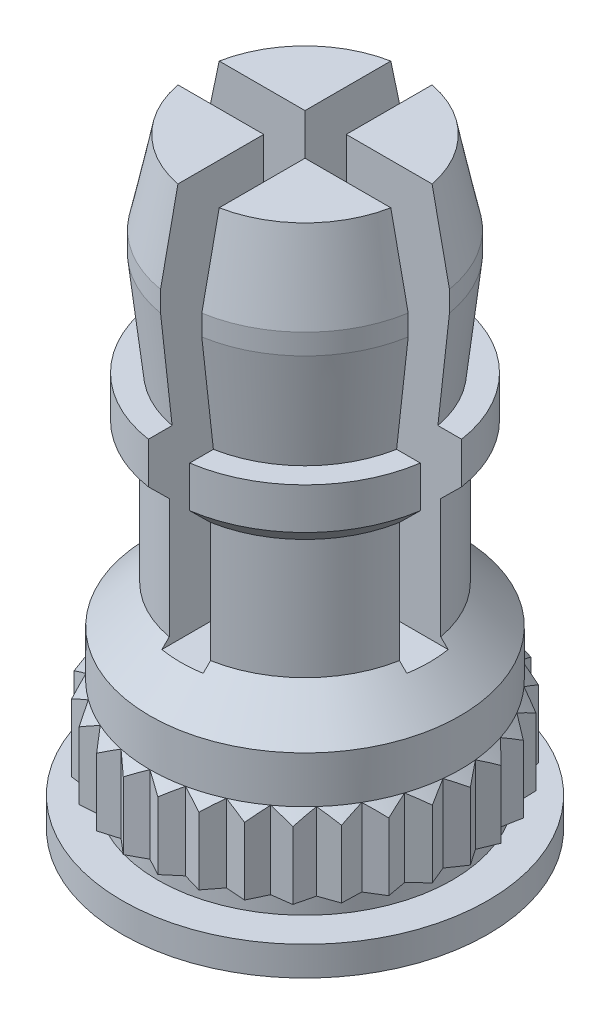
SolidWorks part; units mm, degrees
revolve "Body" add sketch "BodySke" angle 360 about L9 other way angle 12
sketch "BodySke" plane through (0, 0, 0) normal (0, 0, 1) x (1, 0, 0)
  line L0 (2.5578, 0) -> (2.5578, 0.381)
  line L1 (2.6924, 2.5354) -> (2.0295, 3.1984)
  line L2 (2.8702, 1.5494) -> (2.6924, 1.7272)
  line L3 (2.0295, 3.1984) -> (2.0295, 5.2756)
  line L4 (0, -0.508) -> (3.175, -0.508)
  line L5 (3.175, -0.508) -> (3.175, 0)
  line L6 (3.175, 0) -> (2.5578, 0)
  line L7 (2.3876, 5.6337) -> (2.3876, 6.35)
  line L8 (2.6924, 1.7272) -> (2.6924, 2.5354)
  line L9 (0, -0.508) -> (0, 17.145) construction
  line L10 (2.3876, 6.35) -> (1.9812, 6.35)
  line L11 (1.9812, 6.35) -> (2.1793, 8.1407)
  line L12 (2.1793, 8.1407) -> (2.1793, 8.4988)
  line L13 (2.1793, 8.4988) -> (1.8821, 9.9314)
  line L14 (1.8821, 9.9314) -> (0, 9.9314)
  line L15 (2.5578, 0.381) -> (2.8702, 0.381)
  line L16 (2.8702, 0.381) -> (2.8702, 1.5494)
  line L17 (0, 9.9314) -> (0, -0.508)
  line L19 (2.3876, 5.6337) -> (2.0295, 5.2756)
  dimension "Clinch_dia" = 5.7404
  dimension "T_ht" = 0.508
  dimension "D4" = 45
ref_plane "Plane1" through (0, 0, 0) normal (0, 0, 1) x (1, 0, 0)
ref_plane "Plane2" through (0, 0, 0) normal (0, 1, 0) x (1, 0, 0)
ref_plane "Plane3" through (0, 0, 0) normal (1, 0, 0) x (0, 0, -1)
sketch "SlitCutSke" plane through (0, 9.9314, 0) normal (0, 1, 0) x (-1, 0, 0)
  line L0 (-2.6685, 0.3581) -> (2.6685, 0.3581)
  line L1 (2.6685, -0.3581) -> (-2.6685, -0.3581)
  line L2 (-2.6685, 0.3581) -> (-2.6685, -0.3581)
  line L3 (2.6685, 0.3581) -> (2.6685, -0.3581)
  line L4 (-4.064, 0) -> (4.064, 0) construction
  circle A1 centre (0, 0) radius 2.6924 construction
extrude "SlitCut" cut sketch "SlitCutSke" against normal blind 6.86
pattern_circular "SlitCutPat" count 2 every 90 about axis through (0, -0.508, 0) along (0, 1, 0) of "SlitCut"
ref_plane "Plane4" through (0, -0.5486, 0) normal (0, 1, 0) x (-1, 0, 0)
sketch "CliRinCutSke" plane through (0, 0.381, 0) normal (0, -1, 0) x (1, 0, 0)
  line L0 (0.3, 2.8545) -> (0, 2.6924)
  line L1 (0, 2.6924) -> (-0.3, 2.8545)
  line L2 (0, 0) -> (0, 5.842) construction
  arc A1 (0.3, 2.8545) -> (-0.3, 2.8545) centre (0, 0) ccw
  circle A2 centre (0, 0) radius 2.6924 construction
  dimension "Clinch_dia" = 5.7404
  dimension "Angle" = 12
extrude "ClinchCut" cut sketch "CliRinCutSke" against normal blind 1.3462
pattern_circular "ClinchCutPat" count 30 every 12 about axis through (0, -0.508, 0) along (0, 1, 0) of "ClinchCut"
equation "' \"Panel_dia@BodySke\" = 0.156"
equation "' \"Length@BodySke\" = 0.25"
equation "' \"B_dia@BodySke\" = 0.188"
equation "' \"C_dia@BodySke\" = 0.212"
equation "' \"D_ht@BodySke\" = 0.141"
equation "' \"H_dia@BodySke\" = 0.25"
equation "' \"T_ht@BodySke\" = 0.02"
equation "' \"Clinch_dia@BodySke\" = 0.226"
equation "\"Tip_dia@BodySke\" = \"Panel_dia@BodySke\" * 0.95"
equation "\"Slip_dia@BodySke\" = \"Panel_dia@BodySke\" * 1.1"
equation "\"Slip_ht@BodySke\" = \"D_ht@BodySke\" * 0.1"
equation "\"Grip_ht@BodySke\" = \"D_ht@BodySke\" * 0.5"
equation "\"B_ht@BodySke\" = \"B_dia@BodySke\" * 0.15"
equation "\"Neck_dia@BodySke\" = \"B_dia@BodySke\" * 0.85"
equation "\"Neck_len@BodySke\" = \"B_dia@BodySke\" * 0.66"
equation "\"Groove_dia@BodySke\" = \"C_dia@BodySke\" * 0.95"
equation "\"Groove_wid@BodySke\" = \"T_ht@BodySke\" * 0.75"
equation "\"Width@SlitCutSke\" = \"B_ht@BodySke\""
equation "\"Depth@SlitCut\" = \"D_ht@BodySke\" + \"Neck_len@BodySke\" + 0.005"
equation "\"Clinch_lim@BodySke\" = \"C_dia@BodySke\" * 0.25"
equation "\"Count@ClinchCutPat\" = 30"
equation "\"Angle@ClinchCutPat\" = 360 / \"Count@ClinchCutPat\""
equation "\"Angle@CliRinCutSke\" = 360 / \"Count@ClinchCutPat\""
equation "\"Clinch_dia@CliRinCutSke\" = \"Clinch_dia@BodySke\""
equation "\"Clinch_minor@CliRinCutSke\" = \"C_dia@BodySke\""
equation "\"Depth@ClinchCut\" = \"Clinch_lim@BodySke\""
